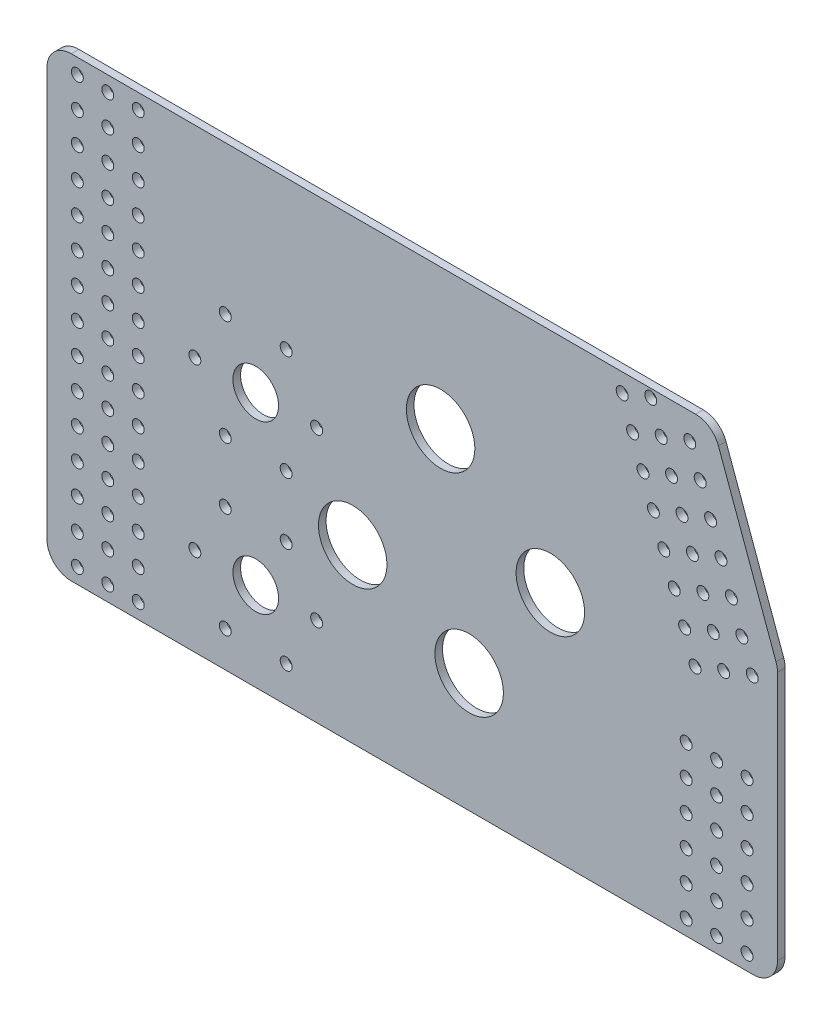
SolidWorks part; units mm, degrees
ref_plane "Front Plane" through (0, 0, 0) normal (0, 0, 1) x (1, 0, 0)
ref_plane "Top Plane" through (0, 0, 0) normal (0, 1, 0) x (1, 0, 0)
ref_plane "Right Plane" through (0, 0, 0) normal (1, 0, 0) x (0, 0, -1)
sketch "Sketch1" plane through (0, 0, 0) normal (0, 0, 1) x (1, 0, 0)
  line B0 (-152.4, 0) -> (152.4, 0)
  line B1 (152.4, 0) -> (152.4, 116.0843)
  line B2 (152.4, 116.0843) -> (125.3149, 190.5)
  line B3 (125.3149, 190.5) -> (-152.4, 190.5)
  line B4 (-152.4, 190.5) -> (-152.4, 0)
  circle B5 centre (-139.7, 184.15) radius 2.4892
  circle B6 centre (-127, 184.15) radius 2.4892
  circle B7 centre (-114.3, 184.15) radius 2.4892
  circle B8 centre (-127, 171.45) radius 2.4892
  circle B9 centre (-114.3, 171.45) radius 2.4892
  circle B10 centre (-127, 158.75) radius 2.4892
  circle B11 centre (-114.3, 158.75) radius 2.4892
  circle B12 centre (-127, 146.05) radius 2.4892
  circle B13 centre (-114.3, 146.05) radius 2.4892
  circle B14 centre (-127, 133.35) radius 2.4892
  circle B15 centre (-114.3, 133.35) radius 2.4892
  circle B16 centre (-127, 120.65) radius 2.4892
  circle B17 centre (-114.3, 120.65) radius 2.4892
  circle B18 centre (-127, 107.95) radius 2.4892
  circle B19 centre (-114.3, 107.95) radius 2.4892
  circle B20 centre (-127, 95.25) radius 2.4892
  circle B21 centre (-114.3, 95.25) radius 2.4892
  circle B22 centre (-127, 82.55) radius 2.4892
  circle B23 centre (-114.3, 82.55) radius 2.4892
  circle B24 centre (-127, 69.85) radius 2.4892
  circle B25 centre (-114.3, 69.85) radius 2.4892
  circle B26 centre (-127, 57.15) radius 2.4892
  circle B27 centre (-114.3, 57.15) radius 2.4892
  circle B28 centre (-127, 44.45) radius 2.4892
  circle B29 centre (-114.3, 44.45) radius 2.4892
  circle B30 centre (-127, 31.75) radius 2.4892
  circle B31 centre (-114.3, 31.75) radius 2.4892
  circle B32 centre (-127, 19.05) radius 2.4892
  circle B33 centre (-114.3, 19.05) radius 2.4892
  circle B34 centre (-127, 6.35) radius 2.4892
  circle B35 centre (-114.3, 6.35) radius 2.4892
  circle B36 centre (-139.7, 171.45) radius 2.4892
  circle B37 centre (-139.7, 158.75) radius 2.4892
  circle B38 centre (-139.7, 146.05) radius 2.4892
  circle B39 centre (-139.7, 133.35) radius 2.4892
  circle B40 centre (-139.7, 120.65) radius 2.4892
  circle B41 centre (-139.7, 107.95) radius 2.4892
  circle B42 centre (-139.7, 95.25) radius 2.4892
  circle B43 centre (-139.7, 82.55) radius 2.4892
  circle B44 centre (-139.7, 69.85) radius 2.4892
  circle B45 centre (-139.7, 57.15) radius 2.4892
  circle B46 centre (-139.7, 44.45) radius 2.4892
  circle B47 centre (-139.7, 31.75) radius 2.4892
  circle B48 centre (-139.7, 19.05) radius 2.4892
  circle B49 centre (-139.7, 6.35) radius 2.4892
  circle B50 centre (87.5907, 182.7494) radius 2.4892
  circle B51 centre (99.5248, 187.093) radius 2.4892
  circle B52 centre (115.8026, 179.5026) radius 2.4892
  circle B53 centre (91.9344, 170.8153) radius 2.4892
  circle B54 centre (103.8685, 175.1589) radius 2.4892
  circle B55 centre (120.1462, 167.5685) radius 2.4892
  circle B56 centre (96.278, 158.8812) radius 2.4892
  circle B57 centre (108.2121, 163.2248) radius 2.4892
  circle B58 centre (124.4899, 155.6344) radius 2.4892
  circle B59 centre (100.6217, 146.9471) radius 2.4892
  circle B60 centre (112.5558, 151.2907) radius 2.4892
  circle B61 centre (128.8335, 143.7003) radius 2.4892
  circle B62 centre (104.9653, 135.013) radius 2.4892
  circle B63 centre (116.8994, 139.3566) radius 2.4892
  circle B64 centre (133.1772, 131.7662) radius 2.4892
  circle B65 centre (109.309, 123.0789) radius 2.4892
  circle B66 centre (121.2431, 127.4226) radius 2.4892
  circle B67 centre (137.5208, 119.8321) radius 2.4892
  circle B68 centre (113.6526, 111.1448) radius 2.4892
  circle B69 centre (125.5867, 115.4885) radius 2.4892
  circle B70 centre (141.8645, 107.898) radius 2.4892
  circle B71 centre (117.9963, 99.2107) radius 2.4892
  circle B72 centre (129.9304, 103.5544) radius 2.4892
  circle B73 centre (146.2081, 95.9639) radius 2.4892
  circle B74 centre (114.3, 69.85) radius 2.4892
  circle B75 centre (127, 69.85) radius 2.4892
  circle B76 centre (139.7, 69.85) radius 2.4892
  circle B77 centre (114.3, 57.15) radius 2.4892
  circle B78 centre (127, 57.15) radius 2.4892
  circle B79 centre (139.7, 57.15) radius 2.4892
  circle B80 centre (114.3, 44.45) radius 2.4892
  circle B81 centre (127, 44.45) radius 2.4892
  circle B82 centre (139.7, 44.45) radius 2.4892
  circle B83 centre (114.3, 31.75) radius 2.4892
  circle B84 centre (127, 31.75) radius 2.4892
  circle B85 centre (139.7, 31.75) radius 2.4892
  circle B86 centre (114.3, 19.05) radius 2.4892
  circle B87 centre (127, 19.05) radius 2.4892
  circle B88 centre (139.7, 19.05) radius 2.4892
  circle B89 centre (114.3, 6.35) radius 2.4892
  circle B90 centre (127, 6.35) radius 2.4892
  circle B91 centre (139.7, 6.35) radius 2.4892
  circle B92 centre (11.8508, 132.0168) radius 14.2875
  circle B93 centre (-24.8197, 71.7449) radius 14.2875
  circle B94 centre (57.6351, 95.7125) radius 14.2875
  circle B95 centre (23.7546, 49.6787) radius 14.2875
  circle B96 centre (-65.2702, 36.9534) radius 9.525
  circle B97 centre (-65.2702, 106.5494) radius 9.525
  circle B98 centre (-65.2702, 131.9494) radius 2.4892
  circle B99 centre (-65.2702, 11.5534) radius 2.4892
  circle B100 centre (-43.2731, 119.2494) radius 2.4892
  circle B101 centre (-43.2731, 93.8494) radius 2.4892
  circle B102 centre (-65.2702, 81.1494) radius 2.4892
  circle B103 centre (-87.2672, 93.8494) radius 2.4892
  circle B104 centre (-87.2672, 119.2494) radius 2.4892
  circle B105 centre (-87.2672, 24.2534) radius 2.4892
  circle B106 centre (-87.2672, 49.6534) radius 2.4892
  circle B107 centre (-65.2702, 62.3534) radius 2.4892
  circle B108 centre (-43.2731, 49.6534) radius 2.4892
  circle B109 centre (-43.2731, 24.2534) radius 2.4892
sketch_block_instance "Block-InnerPlate-1"
sketch_block "Block-InnerPlate" parameters "D1"=4.9784, "D7"=4.9784, "D8"=4.9784, "D9"=4.9784, "D11"=4.9784, "D12"=4.9784, "D13"=4.9784, "D15"=19.05, "D16"=19.05, "D17"=28.575, "D18"=28.575, "D19"=28.575, "D20"=28.575, "D21"=4.9784, "D22"=4.9784, "D2"=6.35, "D3"=12.7, "D4"=12.7, "D5"=12.7, "D6"=6.35, "D10"=12.7, "D14"=12.7, "D23"=25.4, "D24"=25.4
extrude "Boss-Extrude1" add sketch "Sketch1" along normal blind 3.175
sketch "Sketch2" plane through (0, 0, 3.175) normal (0, 0, 1) x (1, 0, 0)
  circle A0 centre (146.2081, 95.9639) radius 2.4892
  dimension "D1" = 4.9784
extrude "Boss-Extrude2" add sketch "Sketch2" against normal blind 3.175
fillet "Fillet1" radius 10.16 5 edges at (-152.4, 0, 1.5875) (152.4, 0, 1.5875) (152.4, 116.0843, 1.5875) (125.3149, 190.5, 1.5875) (-152.4, 190.5, 1.5875)
sketch "Sketch3" plane through (0, 0, 3.175) normal (0, 0, 1) x (1, 0, 0)
  line L0 (-65.2702, 106.5494) -> (-39.8702, 106.5494) construction
  line L1 (-65.2702, 36.9534) -> (-39.8702, 36.9534) construction
  circle A0 centre (-65.2702, 106.5494) radius 9.525
  circle A1 centre (-39.8702, 106.5494) radius 2.4892
  circle A2 centre (-52.5702, 84.5524) radius 2.4892
  circle A3 centre (-77.9702, 84.5524) radius 2.4892
  circle A4 centre (-90.6702, 106.5494) radius 2.4892
  circle A5 centre (-77.9702, 128.5465) radius 2.4892
  circle A6 centre (-52.5702, 128.5465) radius 2.4892
  circle A7 centre (-65.2702, 36.9534) radius 9.525
  circle A8 centre (-39.8702, 36.9534) radius 2.4892
  circle A9 centre (-52.5702, 14.9564) radius 2.4892
  circle A10 centre (-77.9702, 14.9564) radius 2.4892
  circle A11 centre (-90.6702, 36.9534) radius 2.4892
  circle A12 centre (-77.9702, 58.9505) radius 2.4892
  circle A13 centre (-52.5702, 58.9505) radius 2.4892
  dimension "D1" = 19.05
  dimension "D2" = 4.9784
  dimension "D7" = 19.05
  dimension "D8" = 4.9784
  dimension "D3" = 25.4
  dimension "D5" = 25.4
  dimension "D6" = 25.4
  dimension "D9" = 25.4
  dimension "D11" = 25.4
  dimension "D4" = 6
  dimension "D10" = 6
extrude "Cut-Extrude1" cut sketch "Sketch3" against normal blind 3.175
sketch "Sketch4" plane through (0, 0, 3.175) normal (0, 0, 1) x (1, 0, 0)
  circle A0 centre (-65.2702, 131.9494) radius 2.4892
  circle A1 centre (-43.2731, 119.2494) radius 2.4892
  circle A2 centre (-43.2731, 93.8494) radius 2.4892
  circle A3 centre (-65.2702, 81.1494) radius 2.4892
  circle A4 centre (-87.2672, 93.8494) radius 2.4892
  circle A5 centre (-87.2672, 119.2494) radius 2.4892
  circle A6 centre (-65.2702, 62.3534) radius 2.4892
  circle A7 centre (-43.2731, 49.6534) radius 2.4892
  circle A8 centre (-43.2731, 24.2534) radius 2.4892
  circle A9 centre (-65.2702, 11.5534) radius 2.4892
  circle A10 centre (-87.2672, 24.2534) radius 2.4892
  circle A11 centre (-87.2672, 49.6534) radius 2.4892
  dimension "D1" = 4.9784
  dimension "D2" = 4.9784
  dimension "D3" = 4.9784
  dimension "D4" = 4.9784
  dimension "D5" = 4.9784
  dimension "D6" = 4.9784
  dimension "D7" = 4.9784
  dimension "D8" = 4.9784
  dimension "D9" = 4.9784
  dimension "D10" = 4.9784
  dimension "D11" = 4.9784
  dimension "D12" = 4.9784
extrude "Boss-Extrude3" add sketch "Sketch4" against normal blind 3.175
